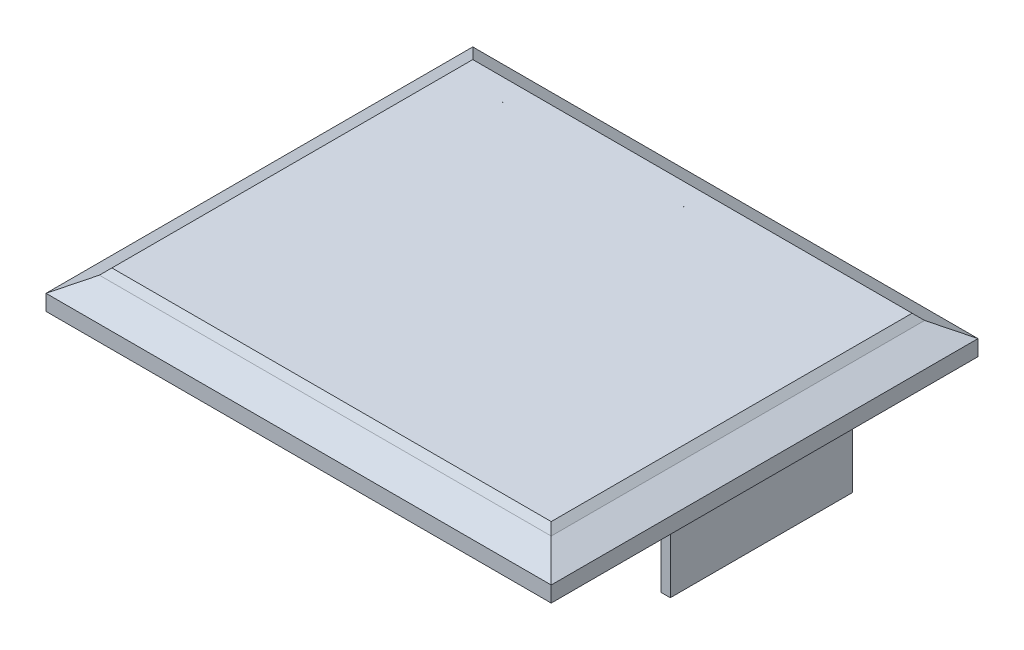
SolidWorks part; units mm, degrees
ref_plane "Front Plane" through (0, 0, 0) normal (0, 0, 1) x (1, 0, 0)
ref_plane "Top Plane" through (0, 0, 0) normal (0, 1, 0) x (1, 0, 0)
ref_plane "Right Plane" through (0, 0, 0) normal (1, 0, 0) x (0, 0, -1)
sketch "Sketch1" plane through (0, 0, 0) normal (0, -1, 0) x (1, 0, 0)
  line L0 (-22.9491, 9.9876) -> (52.0509, 9.9876)
  line L1 (-25.4491, 12.4876) -> (54.5509, 12.4876)
  line L2 (-25.4491, 12.4876) -> (-25.4491, -47.5124)
  line L3 (-25.4491, -47.5124) -> (54.5509, -47.5124)
  line L4 (54.5509, 12.4876) -> (54.5509, -47.5124)
  line L5 (52.0509, 9.9876) -> (52.0509, -45.0124)
  line L6 (-22.9491, -45.0124) -> (52.0509, -45.0124)
  line L7 (-22.9491, 9.9876) -> (-22.9491, -45.0124)
  line L8 (71.971, 48.2689) -> (-84.029, 48.2689)
  line L9 (68.971, 45.2689) -> (-81.029, 45.2689)
  line L10 (68.971, 45.2689) -> (68.971, -79.7311)
  line L11 (68.971, -79.7311) -> (-81.029, -79.7311)
  line L12 (-81.029, 45.2689) -> (-81.029, -79.7311)
  line L13 (-84.029, 48.2689) -> (-84.029, -82.7311)
  line L14 (71.971, -82.7311) -> (-84.029, -82.7311)
  line L15 (71.971, 48.2689) -> (71.971, -82.7311)
  line L16 (-25.4491, -67.5124) -> (54.5509, -67.5124)
  line L17 (-45.6393, -46.3786) -> (-70.6393, -46.3786)
  line L18 (-45.6393, -46.3786) -> (-45.6393, -66.3786)
  line L19 (-45.6393, -66.3786) -> (-70.6393, -66.3786)
  line L20 (-70.6393, -46.3786) -> (-70.6393, -66.3786)
  line L21 (-25.4491, 32.4876) -> (54.5509, 32.4876)
  line L22 (54.5509, 32.4876) -> (54.5509, 12.4876)
  line L23 (-25.4491, 32.4876) -> (-25.4491, 12.4876)
  line L24 (-25.4491, -47.5124) -> (-25.4491, -67.5124)
  line L25 (54.5509, -47.5124) -> (54.5509, -67.5124)
  line L26 (65.971, 42.2689) -> (-78.029, 42.2689)
  line L31 (-17.6571, -79.7311) -> (22.3429, -79.7311)
  line L32 (-17.6571, -79.7311) -> (-17.6571, -82.8953)
  line L33 (-17.6571, -82.8953) -> (22.3429, -82.8953)
  line L34 (22.3429, -79.7311) -> (22.3429, -82.8953)
  line L35 (68.971, 11.3202) -> (71.971, 11.3202)
  line L36 (68.971, 11.3202) -> (68.971, -48.6798)
  line L37 (68.971, -48.6798) -> (71.971, -48.6798)
  line L38 (71.971, 11.3202) -> (71.971, -48.6798)
  line L39 (-78.029, 42.2689) -> (-78.029, -76.7311)
  line L40 (65.971, -76.7311) -> (-78.029, -76.7311)
  line L41 (65.971, 42.2689) -> (65.971, -76.7311)
  line L42 (68.971, -47.6798) -> (71.971, -47.6798)
  line L47 (-81.029, 9.9876) -> (-84.029, 9.9876)
  line L48 (-81.029, 9.9876) -> (-81.029, -20.6346)
  line L49 (-81.029, -20.6346) -> (-84.029, -20.6346)
  line L50 (-84.029, 9.9876) -> (-84.029, -20.6346)
  line L51 (68.971, 10.3202) -> (71.971, 10.3202)
  line L52 (21.3429, -79.7311) -> (21.3429, -82.8953)
  line L53 (-16.6571, -79.7311) -> (-16.6571, -82.8953)
  line L54 (-81.029, 8.9876) -> (-84.029, 8.9876)
  line L55 (-81.029, -19.6346) -> (-84.029, -19.6346)
  line L56 (74.471, 50.7689) -> (-86.529, 50.7689)
  line L57 (-86.529, 50.7689) -> (-86.529, -85.2311)
  line L58 (74.471, -85.2311) -> (-86.529, -85.2311)
  line L59 (74.471, 50.7689) -> (74.471, -85.2311)
  circle A0 centre (-22.9491, 9.9876) radius 1.5
  circle A1 centre (52.0509, 9.9876) radius 1.5
  circle A2 centre (-22.9491, -45.0124) radius 1.5
  circle A3 centre (52.0509, -45.0124) radius 1.5
  circle A4 centre (-45.6393, -46.3786) radius 2.5
  circle A5 centre (-70.6393, -46.3786) radius 2.5
  circle A6 centre (-45.6393, -66.3786) radius 2.5
  circle A7 centre (-70.6393, -66.3786) radius 2.5
  circle A8 centre (-22.9491, -45.0124) radius 4
  circle A9 centre (-22.9491, 9.9876) radius 4
  circle A10 centre (52.0509, 9.9876) radius 4
  circle A11 centre (52.0509, -45.0124) radius 4
  circle A12 centre (65.971, 42.2689) radius 6
  circle A13 centre (-78.029, 42.2689) radius 6
  circle A14 centre (-78.029, -76.7311) radius 6
  circle A15 centre (65.971, -76.7311) radius 6
  dimension "D4" = 125
  dimension "D11" = 2.5
  dimension "D1" = 60
  dimension "D2" = 80
  dimension "D5" = 150
  dimension "D7" = 25
  dimension "D8" = 20
  dimension "D12" = 40
  dimension "D3" = 2.5
  dimension "D6" = 3
  dimension "D9" = 20
  dimension "D10" = 20
  dimension "D13" = 3
  dimension "D14" = 1
  dimension "D15" = 1
  dimension "D16" = 1
  dimension "D17" = 1
  dimension "D18" = 1
  dimension "D19" = 1
  dimension "D20" = 2.5
extrude "Boss-Extrude1" add sketch "Sketch1" against normal blind 5 contours L56 L57 L58 L59
extrude "Boss-Extrude2" add sketch "Sketch1<13>" against normal blind 2 from offset 10 separate body contours L40 L39 L26 L41 offset against normal yes
sketch "Sketch1<13>" plane through (0, 0, 0) normal (0, -1, 0) x (1, 0, 0) same geometry as "Sketch1"
loft "Loft1" add section face at (-6.029, 10, -17.2311) section face at (-6.029, 5, -17.2311) connector at (-78.029, 10, 42.2689) connector at (-86.529, 5, 50.7689)
chamfer "Chamfer1" distance 2 angle 45 4 edges at (-6.029, 12, -76.7311) (-78.029, 12, -17.2311) (-6.029, 12, 42.2689) (65.971, 12, -17.2311)
extrude "Cut-Extrude1" cut sketch "Sketch1<14>" against normal blind 8 contours L26 L39 L40 L41
sketch "Sketch1<14>" plane through (0, 0, 0) normal (0, -1, 0) x (1, 0, 0) same geometry as "Sketch1"
chamfer "Chamfer2" distance 5 angle 45 4 edges at (-6.029, 8, 42.2689) (-78.029, 8, -17.2311) (-6.029, 8, -76.7311) (65.971, 8, -17.2311)
extrude "Boss-Extrude3" add sketch "Sketch1<15>" along normal blind 20 contours L53 L31 L52 L14 | L36 L51 L38 L42 | L48 L55 L50 L54 region at (70.471, 0, -18.6798) region at (-82.529, 0, -5.3235) region at (2.3429, 0, -81.2311)
sketch "Sketch1<15>" plane through (0, 0, 0) normal (0, -1, 0) x (1, 0, 0) same geometry as "Sketch1"
extrude "Cut-Extrude3" cut sketch "Sketch1<18>" against normal blind 5.25 contours A15 | A14 | A13 | A12
sketch "Sketch1<18>" plane through (0, 0, 0) normal (0, -1, 0) x (1, 0, 0) same geometry as "Sketch1"
fillet "Fillet1" radius 2 10 edges at (2.3429, 0, -82.7311) (-84.029, 0, -5.3235) (71.971, 0, -18.6798) (-82.2717, 5.25, 46.5116) (70.2136, 5.25, 46.5116) (-82.2717, 5.25, -80.9737) (70.2136, 5.25, -80.9737) (2.3429, 0, -79.7311) (-81.029, 0, -5.3235) (68.971, 0, -18.6798) conic rho 0.3
